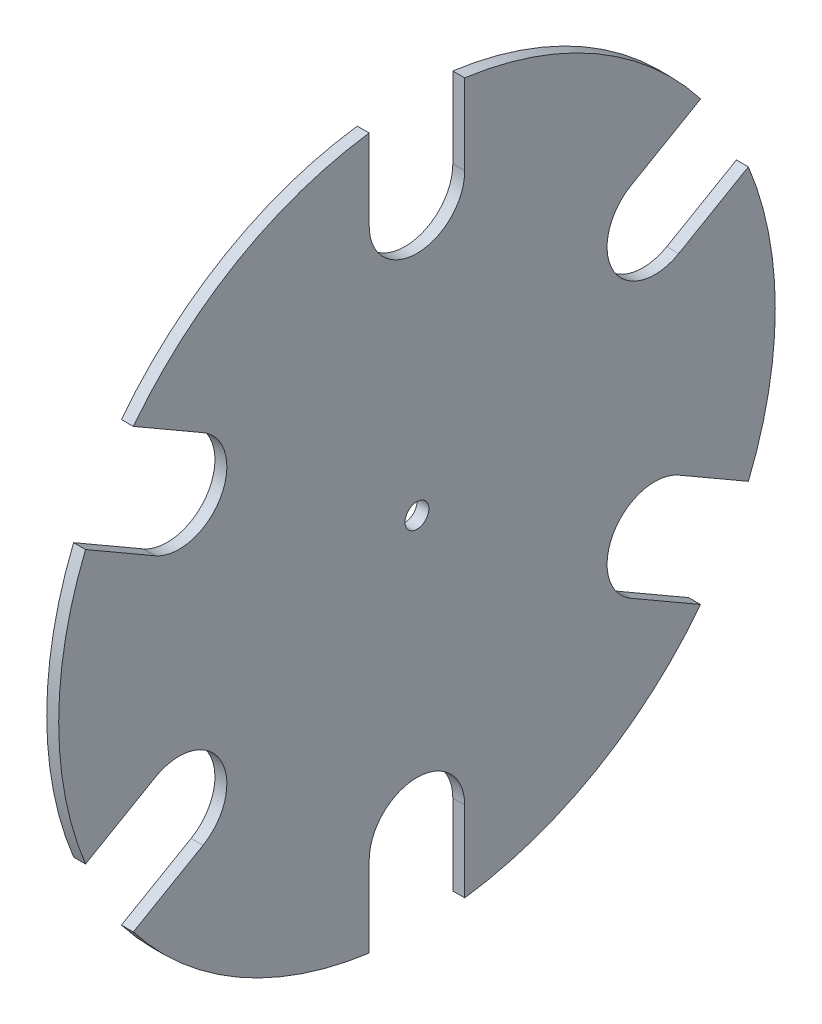
SolidWorks part; units mm, degrees
ref_plane "Front Plane" through (0, 0, 0) normal (0, 0, 1) x (1, 0, 0)
ref_plane "Top Plane" through (0, 0, 0) normal (0, 1, 0) x (1, 0, 0)
ref_plane "Right Plane" through (0, 0, 0) normal (1, 0, 0) x (0, 0, -1)
sketch "Sketch1" plane through (0, 0, 0) normal (1, 0, 0) x (0, 0, -1)
  line L0 (0, 0) -> (0, 300) construction
  line L1 (0, 0) -> (259.8076, 150) construction
  line L2 (0, 0) -> (259.8076, -150) construction
  line L3 (0, 0) -> (0, -300) construction
  line L4 (0, 0) -> (-259.8076, -150) construction
  line L5 (0, 0) -> (-259.8076, 150) construction
  circle A0 centre (0, 0) radius 300
  circle A1 centre (0, 0) radius 10
  circle A2 centre (0, 230) radius 40
  circle A3 centre (199.1858, 115) radius 40
  circle A4 centre (199.1858, -115) radius 40
  circle A5 centre (0, -230) radius 40
  circle A6 centre (-199.1858, -115) radius 40
  circle A7 centre (-199.1858, 115) radius 40
  point P13 (0, 0)
  point P26 (0, 0)
  dimension "D1" = 600
  dimension "D2" = 20
  dimension "D4" = 80
  dimension "D5" = 230
  dimension "D3" = 6
  dimension "D6" = 6
extrude "Boss-Extrude1" add sketch "Sketch1" along normal blind 10
ref_plane "Plane1" through (10, 0, 0) normal (-1, 0, 0) x (0, 0, 1)
sketch "Sketch2" plane through (0, 0, 0) normal (-1, 0, 0) x (0, 0, 1)
  line L0 (40, 297.3214) -> (40, 230)
  line L1 (-40, 297.3214) -> (-40, 230)
  line L2 (0, 230) -> (0, 362.1069) construction
  line L3 (0, 0) -> (0, 230) construction
  line L4 (199.1858, 115) -> (313.5938, 181.0534) construction
  line L5 (0, 0) -> (199.1858, 115) construction
  line L6 (199.1858, -115) -> (313.5938, -181.0534) construction
  line L7 (0, 0) -> (199.1858, -115) construction
  line L8 (0, -230) -> (0, -362.1069) construction
  line L9 (0, 0) -> (0, -230) construction
  line L10 (-199.1858, -115) -> (-313.5938, -181.0534) construction
  line L11 (0, 0) -> (-199.1858, -115) construction
  line L12 (277.4879, 114.0197) -> (219.1858, 80.359)
  line L13 (-237.4879, 183.3017) -> (-179.1858, 149.641)
  line L14 (-277.4879, 114.0197) -> (-219.1858, 80.359)
  line L15 (237.4879, 183.3017) -> (179.1858, 149.641)
  line L16 (237.4879, -183.3017) -> (179.1858, -149.641)
  line L17 (277.4879, -114.0197) -> (219.1858, -80.359)
  line L18 (-40, -297.3214) -> (-40, -230)
  line L19 (40, -297.3214) -> (40, -230)
  line L20 (-277.4879, -114.0197) -> (-219.1858, -80.359)
  line L21 (-237.4879, -183.3017) -> (-179.1858, -149.641)
  arc A0 (40, 297.3214) -> (-40, 297.3214) centre (0, 0) ccw
  arc A1 (-237.4879, 183.3017) -> (-277.4879, 114.0197) centre (0, 0) ccw
  arc A2 (-219.1858, 80.359) -> (-179.1858, 149.641) centre (-199.1858, 115) cw
  arc A3 (-40, 230) -> (40, 230) centre (0, 230) cw
  arc A4 (277.4879, 114.0197) -> (237.4879, 183.3017) centre (0, 0) ccw
  arc A5 (179.1858, 149.641) -> (219.1858, 80.359) centre (199.1858, 115) cw
  arc A6 (237.4879, -183.3017) -> (277.4879, -114.0197) centre (0, 0) ccw
  arc A7 (219.1858, -80.359) -> (179.1858, -149.641) centre (199.1858, -115) cw
  arc A8 (-40, -297.3214) -> (40, -297.3214) centre (0, 0) ccw
  arc A9 (40, -230) -> (-40, -230) centre (0, -230) cw
  arc A10 (-277.4879, -114.0197) -> (-237.4879, -183.3017) centre (0, 0) ccw
  arc A11 (-179.1858, -149.641) -> (-219.1858, -80.359) centre (-199.1858, -115) cw
  point P2 (-256.3898, 148.0267)
  point P16 (0, 0)
  point P22 (0, 296.0534)
  point P28 (256.3898, 148.0267)
  point P34 (256.3898, -148.0267)
  point P40 (0, -296.0534)
  point P46 (-256.3898, -148.0267)
  point P51 (0, 0)
  dimension "D1" = 6
extrude "Cut-Extrude1" cut sketch "Sketch2" against normal blind 10
